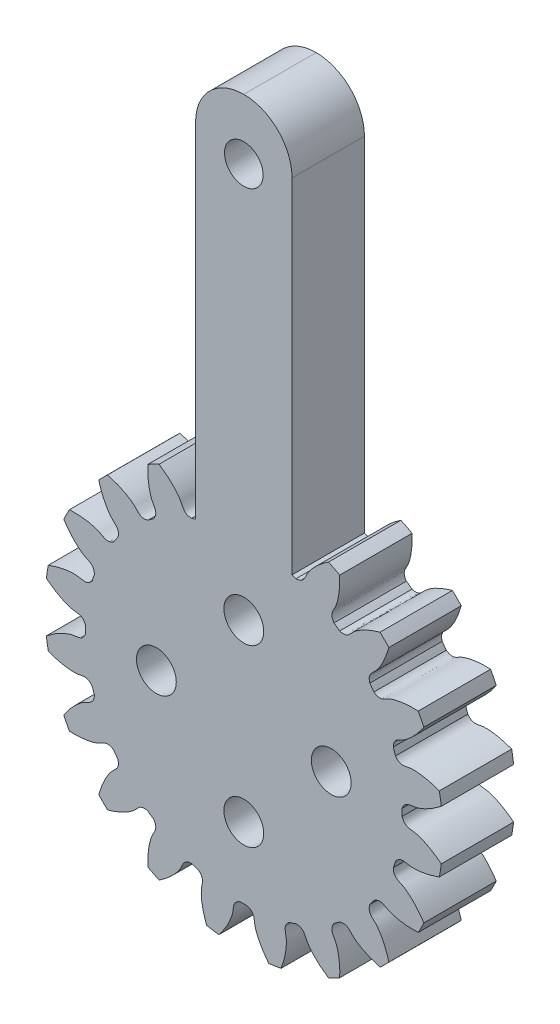
SolidWorks part; units mm, degrees
ref_plane "前视基准面" through (0, 0, 0) normal (0, 0, 1) x (1, 0, 0)
ref_plane "上视基准面" through (0, 0, 0) normal (0, 1, 0) x (1, 0, 0)
ref_plane "右视基准面" through (0, 0, 0) normal (1, 0, 0) x (0, 0, -1)
sketch "草图1" plane through (0, 0, 0) normal (0, 0, 1) x (1, 0, 0)
  circle A0 centre (0, 0) radius 16.5
extrude "凸台-拉伸1" add sketch "草图1" along normal blind 6
ref_axis "基准轴1" through (0, 0, -0.3) along (0, 0, 1)
sketch "草图2" plane through (0, 0, 0) normal (0, 0, 1) x (1, 0, 0)
  line L0 (0, 0) -> (0, 16.5) construction
  circle A0 centre (0, 0) radius 16.5 construction
  arc A1 (0.29, 13.1218) -> (-0.29, 13.1218) centre (0, 0) ccw
  arc A2 (4.7717, 18.7474) -> (-4.7717, 18.7474) centre (0, 0) ccw
  spline S0 degree 3 poles (0.29, 13.1218) (0.9168, 13.3402) (0.8356, 13.7807) (0.9193, 14.205) (0.9283, 14.2463) (0.9395, 14.293) (0.9529, 14.3448) (0.969, 14.4018) (0.9878, 14.4638) (1.0095, 14.5309) (1.0345, 14.6028) (1.0629, 14.6795) (1.0948, 14.7608) (1.1305, 14.8467) (1.1702, 14.9371) (1.2141, 15.0317) (1.2623, 15.1305) (1.315, 15.2334) (1.3725, 15.3401) (1.4349, 15.4506) (1.5023, 15.5646) (1.575, 15.6821) (1.653, 15.8029) (1.7366, 15.9267) (1.826, 16.0534) (1.9211, 16.1829) (2.0223, 16.3149) (2.1296, 16.4493) (2.2432, 16.5859) (2.3632, 16.7244) (2.4897, 16.8646) (2.6229, 17.0065) (2.7628, 17.1496) (2.9095, 17.2939) (3.0632, 17.4391) (3.224, 17.585) (3.3918, 17.7313) (3.567, 17.8779) (3.7493, 18.0245) (3.9391, 18.1709) (4.1363, 18.3167) (4.4122, 18.5125) (4.6259, 18.6545) (4.7717, 18.7474) knots 0 0 0 0 0.165916 0.170906 0.176664 0.183189 0.190482 0.198542 0.207371 0.216967 0.22733 0.238462 0.250361 0.263027 0.276462 0.290664 0.305634 0.321371 0.337876 0.355149 0.37319 0.391998 0.411574 0.431917 0.453028 0.474907 0.497554 0.520968 0.54515 0.570099 0.595817 0.622302 0.649554 0.677575 0.706363 0.735918 0.766242 0.797333 0.829191 0.861818 0.895212 0.929373 1 1 1 1
  spline S1 degree 3 poles (-0.29, 13.1218) (-0.9168, 13.3402) (-0.8356, 13.7807) (-0.9193, 14.205) (-0.9283, 14.2463) (-0.9395, 14.293) (-0.9529, 14.3448) (-0.969, 14.4018) (-0.9878, 14.4638) (-1.0095, 14.5309) (-1.0345, 14.6028) (-1.0629, 14.6795) (-1.0948, 14.7608) (-1.1305, 14.8467) (-1.1702, 14.9371) (-1.2141, 15.0317) (-1.2623, 15.1305) (-1.315, 15.2334) (-1.3725, 15.3401) (-1.4349, 15.4506) (-1.5023, 15.5646) (-1.575, 15.6821) (-1.653, 15.8029) (-1.7366, 15.9267) (-1.826, 16.0534) (-1.9211, 16.1829) (-2.0223, 16.3149) (-2.1296, 16.4493) (-2.2432, 16.5859) (-2.3632, 16.7244) (-2.4897, 16.8646) (-2.6229, 17.0065) (-2.7628, 17.1496) (-2.9095, 17.2939) (-3.0632, 17.4391) (-3.224, 17.585) (-3.3918, 17.7313) (-3.567, 17.8779) (-3.7493, 18.0245) (-3.9391, 18.1709) (-4.1363, 18.3167) (-4.4122, 18.5125) (-4.6259, 18.6545) (-4.7717, 18.7474) knots 0 0 0 0 0.165916 0.170906 0.176664 0.183189 0.190482 0.198542 0.207371 0.216967 0.22733 0.238462 0.250361 0.263027 0.276462 0.290664 0.305634 0.321371 0.337876 0.355149 0.37319 0.391998 0.411574 0.431917 0.453028 0.474907 0.497554 0.520968 0.54515 0.570099 0.595817 0.622302 0.649554 0.677575 0.706363 0.735918 0.766242 0.797333 0.829191 0.861818 0.895212 0.929373 1 1 1 1
extrude "切除-拉伸1" cut sketch "草图2" along normal through all
pattern_circular "阵列(圆周)1" count 20 every 18 about axis through (0, 0, -0.3) along (0, 0, 1) of "切除-拉伸1"
sketch "草图3" plane through (0, 0, 0) normal (0, 0, 1) x (1, 0, 0)
  circle A0 centre (0, 0) radius 15 construction
  dimension "Dn" = 30
sketch "草图5" plane through (0, 0, 0) normal (0, 0, -1) x (-1, 0, 0)
  circle A0 centre (0, 0) radius 10.75
  dimension "D1" = 21.5
extrude "切除-拉伸2" cut sketch "草图5" against normal blind 0.01
sketch "草图6" plane through (0, 0, 0.01) normal (0, 0, -1) x (-1, 0, 0)
  circle A0 centre (0, 0) radius 4.75
  dimension "D1" = 9.5
sketch "草图7" plane through (0, 0, 0.01) normal (0, 0, -1) x (-1, 0, 0)
  line L0 (3.3, 0) -> (-3.3, 0) construction
  line L1 (0, 3.3) -> (0, -3.3) construction
  circle A0 centre (0, 7.25) radius 0.75
  circle A1 centre (7.25, 0) radius 0.75
  circle A2 centre (0, -7.25) radius 0.75
  circle A3 centre (-7.25, 0) radius 0.75
  dimension "D3" = 1.5
  dimension "D4" = 1.5
  dimension "D1" = 7.25
  dimension "D2" = 7.25
extrude "切除-拉伸4" cut sketch "草图7" against normal blind 3
sketch "草图8" plane through (0, 0, 0) normal (0, 0, -1) x (-1, 0, 0)
  line L0 (0, 0) -> (0, 23.1948) construction
  line L2 (-4, 50) -> (4, 50)
  line L3 (-4, 50) -> (-4, 11.5651)
  line L4 (-4, 11.5651) -> (4, 11.5651)
  line L5 (4, 50) -> (4, 11.5651)
  line L6 (-4, 50) -> (4, 11.5651) construction
  line L7 (-4, 11.5651) -> (4, 50) construction
  point P3 (0, 30.7826)
  dimension "D1" = 8
  dimension "D2" = 50
extrude "凸台-拉伸2" add sketch "草图8" against normal up to surface (6 mm away) up to face at (0, 0, 6)
sketch "草图9" plane through (0, 0, 0) normal (0, 0, -1) x (-1, 0, 0)
  line L0 (4, 12.5006) -> (4, 50) construction
  line L1 (-4, 50) -> (4, 50)
  line L2 (-4, 50) -> (-4, 45)
  line L3 (-4, 45) -> (4, 45)
  line L4 (4, 50) -> (4, 45)
  circle A0 centre (0, 40) radius 1.6
  dimension "D3" = 3.2
  dimension "D1" = 40
  dimension "D2" = 5
extrude "切除-拉伸5" cut sketch "草图9" against normal blind 10
fillet "圆角1" radius 4 2 edges at (4, 45, 3) (-4, 45, 3)
sketch "草图10" plane through (0, 0, 6) normal (0, 0, 1) x (1, 0, 0)
  circle A0 centre (0, 7.25) radius 1.65
  circle A1 centre (7.25, 0) radius 1.65
  circle A2 centre (0, -7.25) radius 1.65
  circle A3 centre (-7.25, 0) radius 1.65
extrude "切除-拉伸6" cut sketch "草图10" against normal through all
